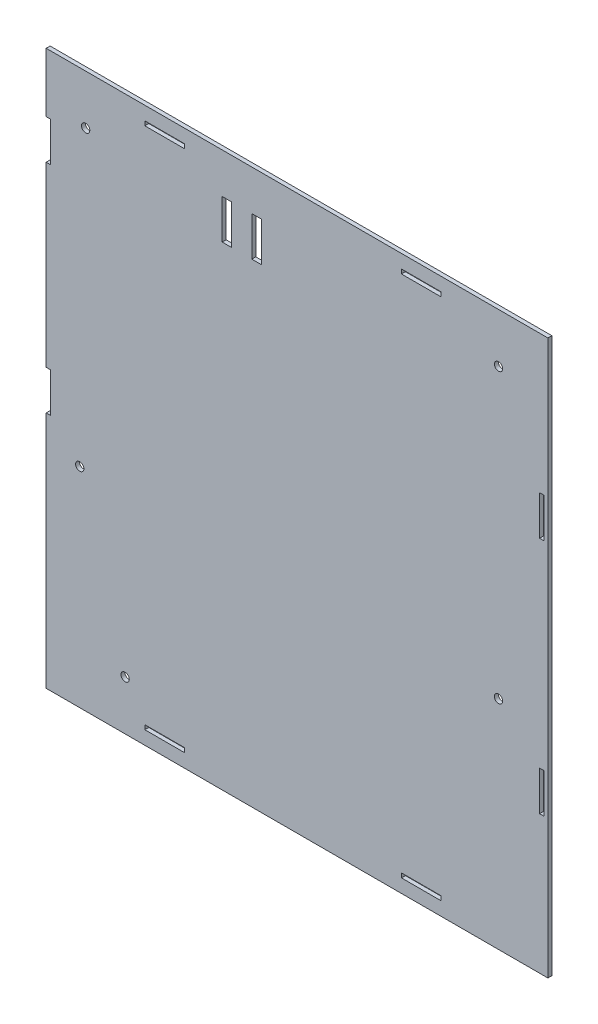
SolidWorks part; units mm, degrees
material "Acrylic (Medium-high impact)"
ref_plane "Front Plane" through (0, 0, 0) normal (0, 0, 1) x (1, 0, 0)
ref_plane "Top Plane" through (0, 0, 0) normal (0, 1, 0) x (1, 0, 0)
ref_plane "Right Plane" through (0, 0, 0) normal (1, 0, 0) x (0, 0, -1)
sketch "Sketch1" plane through (0, 0, 0) normal (0, 0, 1) x (1, 0, 0)
  line L0 (-70, 268.6) -> (-50, 268.6)
  line L1 (-250, -5.4333) -> (4.2, -5.4333)
  line L2 (-250, -5.4333) -> (-250, 275.4333)
  line L3 (-250, 275.4333) -> (4.2, 275.4333)
  line L4 (4.2, -5.4333) -> (4.2, 275.4333)
  line L5 (2, 275.4333) -> (0, 275.4333) construction
  line L6 (-70, 268.6) -> (-70, 266.4)
  line L7 (-70, 266.4) -> (-50, 266.4)
  line L8 (-250, 135) -> (4.2, 135) construction
  line L9 (-50, 268.6) -> (-50, 266.4)
  line L10 (-70, 267.5) -> (-50, 267.5) construction
  line L11 (-60, 268.6) -> (-60, 266.4) construction
  line L12 (-190, 1.4) -> (-190, 3.6) construction
  line L13 (2.2, 74.5667) -> (0, 74.5667) construction
  line L14 (1.1, 64.5667) -> (1.1, 84.5667) construction
  line L15 (2.2, 64.5667) -> (2.2, 84.5667)
  line L16 (0, 84.5667) -> (2.2, 84.5667)
  line L17 (0, 64.5667) -> (0, 84.5667)
  line L18 (0, 64.5667) -> (2.2, 64.5667)
  line L19 (-200, 2.5) -> (-180, 2.5) construction
  line L20 (-60, 1.4) -> (-60, 3.6) construction
  line L21 (-70, 2.5) -> (-50, 2.5) construction
  line L22 (-180, 1.4) -> (-180, 3.6)
  line L23 (-200, 3.6) -> (-180, 3.6)
  line L24 (-200, 1.4) -> (-200, 3.6)
  line L25 (0, 205.4333) -> (2, 205.4333) construction
  line L26 (0, 205.4333) -> (2.2, 205.4333)
  line L27 (0, 205.4333) -> (0, 185.4333)
  line L28 (0, 185.4333) -> (2.2, 185.4333)
  line L29 (2.2, 205.4333) -> (2.2, 185.4333)
  line L30 (0, 205.4333) -> (2, 205.4333) construction
  line L31 (-200, 1.4) -> (-180, 1.4)
  line L32 (-50, 1.4) -> (-50, 3.6)
  line L33 (-70, 3.6) -> (-50, 3.6)
  line L34 (-200, 268.6) -> (-180, 268.6)
  line L35 (-200, 268.6) -> (-200, 266.4)
  line L36 (-200, 266.4) -> (-180, 266.4)
  line L37 (-180, 268.6) -> (-180, 266.4)
  line L38 (-70, 1.4) -> (-70, 3.6)
  line L39 (-70, 1.4) -> (-50, 1.4)
  line L47 (2, -5.4333) -> (0, -5.4333) construction
  line L48 (-250, 2) -> (-250, 0) construction
  line L49 (-200, 267.5) -> (-180, 267.5) construction
  line L50 (-190, 268.6) -> (-190, 266.4) construction
  line L51 (1.1, 205.4333) -> (1.1, 185.4333) construction
  line L52 (2.2, 195.4333) -> (0, 195.4333) construction
  point P4 (1.1, 205.4333)
  point P5 (0, 195.4333)
  point P6 (-200, 267.5)
  point P9 (-250, 135)
  point P10 (-122.9, -5.4333)
  point P11 (4.2, 135)
  point P12 (-122.9, 275.4333)
  point P17 (-70, 267.5)
  point P22 (-50, 267.5)
  point P23 (-60, 268.6)
  point P24 (-60, 266.4)
  point P29 (-60, 267.5)
  point P43 (2.2, 195.4333)
  point P46 (1.1, 185.4333)
  point P55 (1.1, 195.4333)
  point P60 (1.1, 74.5667)
  point P61 (1.1, 84.5667)
  point P62 (2.2, 74.5667)
  point P63 (0, 74.5667)
  point P64 (1.1, 64.5667)
  point P71 (-180, 267.5)
  point P72 (-190, 268.6)
  point P73 (-190, 266.4)
  point P78 (-190, 267.5)
  point P88 (-190, 2.5)
  point P89 (-190, 3.6)
  point P90 (-190, 1.4)
  point P91 (-180, 2.5)
  point P92 (-60, 2.5)
  point P93 (-60, 3.6)
  point P94 (-60, 1.4)
  point P95 (-50, 2.5)
  point P96 (-70, 2.5)
  point P97 (-200, 2.5)
  dimension "D2" = 50
  dimension "D3" = 250
  dimension "D4" = 2
  dimension "D5" = 110
  dimension "D6" = 2
  dimension "D10" = 2.2
  dimension "D11" = 20
  dimension "D14" = 7.9333
  dimension "D17" = 20
extrude "Boss-Extrude1" add sketch "Sketch1" along normal blind 2
sketch "Sketch2" plane through (0, 0, 2) normal (0, 0, 1) x (1, 0, 0)
  line L0 (-145.9052, 255) -> (-140.9052, 255) construction
  line L1 (-145.8052, 255) -> (-141.0052, 255)
  line L2 (-145.8052, 255) -> (-145.8052, 235)
  line L3 (-145.8052, 235) -> (-141.0052, 235)
  line L4 (-141.0052, 255) -> (-141.0052, 235)
  line L5 (-145.9052, 235) -> (-140.9052, 235) construction
  line L6 (-145.9052, 235) -> (-145.9052, 255) construction
  line L8 (-156.0052, 235) -> (-160.8052, 235)
  line L9 (-156.0052, 235) -> (-156.0052, 255)
  line L10 (-156.0052, 255) -> (-160.8052, 255)
  line L11 (-160.8052, 235) -> (-160.8052, 255)
  dimension "D1" = 4.8
  dimension "D2" = 0.1
  dimension "D3" = 4.8
  dimension "D4" = 15
extrude "Cut-Extrude1" cut sketch "Sketch2" against normal blind 5
sketch "Sketch3" plane through (0, 0, 2) normal (0, 0, 1) x (1, 0, 0)
  line L0 (4.2, 275.4333) -> (-250, 275.4333) construction
  line L1 (-250, 275.4333) -> (-250, -5.4333) construction
  line L2 (4.2, -5.4333) -> (4.2, 275.4333) construction
  circle A0 centre (-230, 250.4333) radius 2.1
  circle A1 centre (-20.8, 250.4333) radius 2.1
  dimension "D1" = 4.2
  dimension "D2" = 4.2
  dimension "D3" = 25
  dimension "D4" = 20
  dimension "D5" = 25
  dimension "D6" = 25
extrude "Cut-Extrude2" cut sketch "Sketch3" against normal blind 5
sketch "Sketch4" plane through (0, 0, 2) normal (0, 0, 1) x (1, 0, 0)
  line L0 (-250, -5.4333) -> (4.2, -5.4333) construction
  line L1 (-250, 275.4333) -> (-250, -5.4333) construction
  circle A0 centre (-210, 19.5667) radius 2.1
  dimension "D1" = 25
  dimension "D2" = 40
  dimension "D3" = 4.2
extrude "Cut-Extrude3" cut sketch "Sketch4" against normal blind 5
sketch "Sketch5" plane through (0, 0, 2) normal (0, 0, 1) x (1, 0, 0)
  line L0 (4.2, -5.4333) -> (4.2, 275.4333) construction
  line L1 (-250, -5.4333) -> (4.2, -5.4333) construction
  circle A0 centre (-20.8, 104.5667) radius 2.1
  dimension "D1" = 4.2
  dimension "D2" = 25
  dimension "D3" = 110
extrude "Cut-Extrude4" cut sketch "Sketch5" against normal blind 5
sketch "Sketch6" plane through (0, 0, 2) normal (0, 0, 1) x (1, 0, 0)
  circle A0 centre (-233, 100.4333) radius 2.1
  dimension "D1" = 4.2
extrude "Cut-Extrude5" cut sketch "Sketch6" against normal blind 5
sketch "Sketch7" plane through (0, 0, 2) normal (0, 0, 1) x (1, 0, 0)
  line L1 (-250, 245.4333) -> (-247.8, 245.4333)
  line L2 (-250, 245.4333) -> (-250, 225.4333)
  line L3 (-250, 225.4333) -> (-247.8, 225.4333)
  line L4 (-247.8, 245.4333) -> (-247.8, 225.4333)
  line L5 (-250, 135.4333) -> (-247.8, 135.4333)
  line L6 (-250, 135.4333) -> (-250, 115.4333)
  line L7 (-250, 115.4333) -> (-247.8, 115.4333)
  line L8 (-247.8, 135.4333) -> (-247.8, 115.4333)
  dimension "D1" = 20
  dimension "D2" = 2.2
  dimension "D4" = 20
extrude "Cut-Extrude6" cut sketch "Sketch7" against normal blind 10
